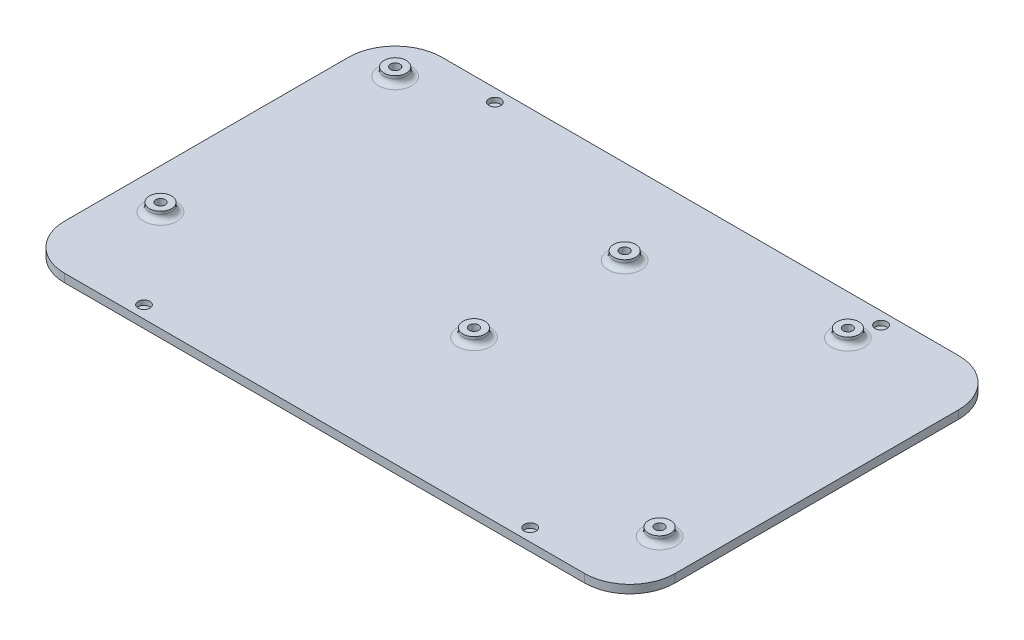
SolidWorks part; units mm, degrees
material "ABS"
ref_plane "Front Plane" through (0, 0, 0) normal (0, 0, 1) x (1, 0, 0)
ref_plane "Top Plane" through (0, 0, 0) normal (0, 1, 0) x (1, 0, 0)
ref_plane "Right Plane" through (0, 0, 0) normal (1, 0, 0) x (0, 0, -1)
sketch "Sketch1" plane through (0, 0, 0) normal (0, 1, 0) x (1, 0, 0)
  line L1 (0, 0) -> (-201.28, 0)
  line L2 (0, 0) -> (0, 116.21)
  line L3 (0, 116.21) -> (-201.28, 116.21)
  line L4 (-201.28, 0) -> (-201.28, 116.21)
  dimension "D1" = 201.28
  dimension "D2" = 116.21
extrude "Boss-Extrude1" add sketch "Sketch1" against normal blind 3
fillet "Fillet1" radius 6.98 2 edges at (0, -1.5, -116.21) (-201.28, -1.5, -116.21)
fillet "Fillet2" radius 6.35 2 edges at (0, -1.5, 0) (-201.28, -1.5, 0)
sketch "Sketch2" plane through (0, -3, 0) normal (0, -1, 0) x (-1, 0, 0)
  line L8 (6.35, -10) -> (194.93, -10)
  line L9 (-10, 109.23) -> (-10, 6.35)
  line L10 (194.3, 126.21) -> (6.98, 126.21)
  line L11 (211.28, 6.35) -> (211.28, 109.23)
  line L12 (6.35, -10) -> (194.93, -10)
  line L13 (-10, 109.23) -> (-10, 6.35)
  line L14 (194.3, 126.21) -> (6.98, 126.21)
  line L15 (211.28, 6.35) -> (211.28, 109.23)
  line L16 (6.35, 0) -> (194.93, 0)
  line L17 (0, 109.23) -> (0, 6.35)
  line L18 (194.3, 116.21) -> (6.98, 116.21)
  line L19 (201.28, 6.35) -> (201.28, 109.23)
  line L20 (6.35, 0) -> (194.93, 0)
  line L21 (0, 109.23) -> (0, 6.35)
  line L22 (194.3, 116.21) -> (6.98, 116.21)
  line L23 (201.28, 6.35) -> (201.28, 109.23)
  arc A8 (-10, 6.35) -> (6.35, -10) centre (6.35, 6.35) ccw
  arc A9 (6.98, 126.21) -> (-10, 109.23) centre (6.98, 109.23) ccw
  arc A10 (211.28, 109.23) -> (194.3, 126.21) centre (194.3, 109.23) ccw
  arc A11 (194.93, -10) -> (211.28, 6.35) centre (194.93, 6.35) ccw
  arc A12 (-10, 6.35) -> (6.35, -10) centre (6.35, 6.35) ccw
  arc A13 (6.98, 126.21) -> (-10, 109.23) centre (6.98, 109.23) ccw
  arc A14 (211.28, 109.23) -> (194.3, 126.21) centre (194.3, 109.23) ccw
  arc A15 (194.93, -10) -> (211.28, 6.35) centre (194.93, 6.35) ccw
  arc A16 (0, 6.35) -> (6.35, 0) centre (6.35, 6.35) ccw
  arc A17 (6.98, 116.21) -> (0, 109.23) centre (6.98, 109.23) ccw
  arc A18 (201.28, 109.23) -> (194.3, 116.21) centre (194.3, 109.23) ccw
  arc A19 (194.93, 0) -> (201.28, 6.35) centre (194.93, 6.35) ccw
  arc A20 (0, 6.35) -> (6.35, 0) centre (6.35, 6.35) ccw
  arc A21 (6.98, 116.21) -> (0, 109.23) centre (6.98, 109.23) ccw
  arc A22 (201.28, 109.23) -> (194.3, 116.21) centre (194.3, 109.23) ccw
  arc A23 (194.93, 0) -> (201.28, 6.35) centre (194.93, 6.35) ccw
  dimension "D1" = 10
  dimension "D2" = 0
extrude "Boss-Extrude3" add sketch "Sketch2" against normal up to surface (3 mm away) up to face at (-100.64, 0, -57.9801)
sketch "Sketch3" plane through (0, 0, 0) normal (0, 1, 0) x (1, 0, 0)
  line L0 (-100.64, -10) -> (-100.64, 126.21) construction
  line L1 (-6.35, -10) -> (-194.93, -10) construction
  line L2 (-194.3, 126.21) -> (-6.98, 126.21) construction
  line L3 (-211.28, 6.35) -> (-211.28, 109.23) construction
  line L6 (-100.64, 58.105) -> (-211.28, 58.105) construction
  line L7 (-100.64, -5.5) -> (-30.64, -5.5) construction
  circle A0 centre (-170.64, -5.5) radius 2.15
  circle A1 centre (-30.64, 121.71) radius 2.15
  circle A2 centre (-30.64, -5.5) radius 2.15
  circle A3 centre (-170.64, 121.71) radius 2.15
  dimension "D1" = 4.5
  dimension "D4" = 4.3
  dimension "D3" = 70
extrude "Cut-Extrude1" cut sketch "Sketch3" against normal blind 1.75
hole_wizard "M3 Clearance Hole2" positions "Sketch7" profile "Sketch5" hole size "M3" standard "ANSI Metric" end condition through all
sketch "Sketch7" plane through (0, 0, 0) normal (0, 1, 0) x (1, 0, 0)
  point P0 (-196.83, 111.76)
  point P3 (-32.71, 111.76)
  point P6 (-97.45, 95.57)
  point P9 (-100.63, 44.13)
  point P12 (-4.45, 15.24)
  point P15 (-196.83, 26.67)
sketch "Sketch5" plane through (-196.83, 0, -111.76) normal (1, 0, 0) x (0, 0, 1)
  line L0 (0, 0) -> (0, 3)
  line L1 (0, 3) -> (1.7, 3)
  line L2 (1.7, 3) -> (1.7, 0)
  line L5 (1.7, 0) -> (0, 0)
  line L11 (0, -6.35) -> (0, 107.95) construction
  dimension "Thru Hole Dia." = 3.4
  dimension "Thru Hole Depth" = 3
sketch "Sketch8" plane through (0, 0, 0) normal (0, 1, 0) x (1, 0, 0)
  circle A0 centre (-196.83, 111.76) radius 4
  circle A1 centre (-196.83, 26.67) radius 4
  circle A2 centre (-100.63, 44.13) radius 4
  circle A3 centre (-4.45, 15.24) radius 4
  circle A4 centre (-97.45, 95.57) radius 4
  circle A5 centre (-32.71, 111.76) radius 4
  dimension "D1" = 8
extrude "Boss-Extrude4" add sketch "Sketch8" along normal blind 3
fillet "Fillet3" radius 2 6 edges at (-32.71, 0, -107.76) (-4.45, 0, -11.24) (-97.45, 0, -91.57) (-100.63, 0, -40.13) (-196.83, 0, -22.67) (-196.83, 0, -107.76)
hole_wizard "M3 Clearance Hole3" positions "Sketch10" profile "Sketch9" hole size "M3" standard "ANSI Metric" end condition up to next
sketch "Sketch10" plane through (0, -3, 0) normal (0, -1, 0) x (-1, 0, 0)
  point P0 (32.71, 111.76)
  point P3 (4.45, 15.24)
  point P6 (100.63, 44.13)
  point P9 (196.83, 26.67)
  point P12 (97.45, 95.57)
  point P15 (196.83, 111.76)
sketch "Sketch9" plane through (-32.71, -3, -111.76) normal (1, 0, 0) x (0, 0, -1)
  line L0 (0, 0) -> (0, 6)
  line L1 (0, 6) -> (1.7, 6)
  line L2 (1.7, 6) -> (1.7, 0)
  line L5 (1.7, 0) -> (0, 0)
  line L11 (0, -6.35) -> (0, 107.95) construction
  dimension "Thru Hole Dia." = 3.4
  dimension "Thru Hole Depth" = 6
